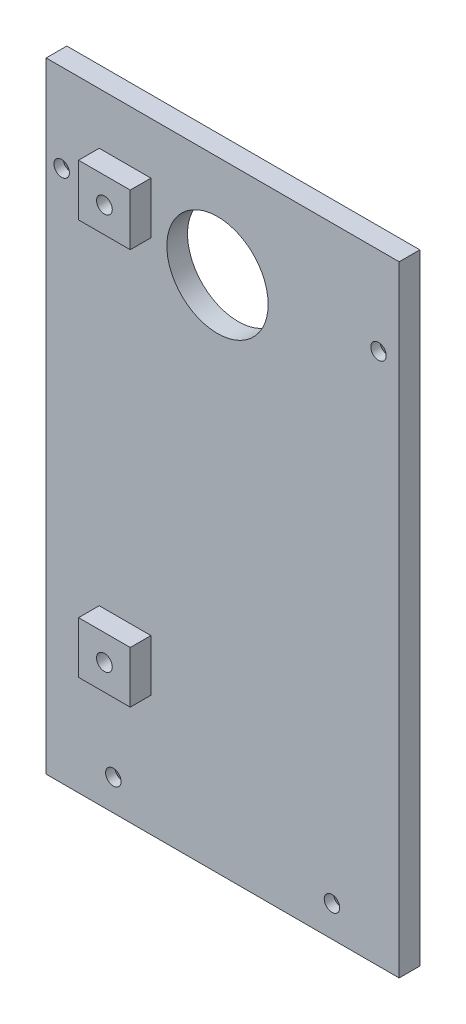
SolidWorks part; units mm, degrees
ref_plane "Front Plane" through (0, 0, 0) normal (0, 0, 1) x (1, 0, 0)
ref_plane "Top Plane" through (0, 0, 0) normal (0, 1, 0) x (1, 0, 0)
ref_plane "Right Plane" through (0, 0, 0) normal (1, 0, 0) x (0, 0, -1)
sketch "Sketch1" plane through (0, 0, 0) normal (0, 0, 1) x (1, 0, 0)
  line L0 (0, 0) -> (0, 30) construction
  line L1 (-16.575, -30) -> (16.575, -30)
  line L2 (-16.575, -30) -> (-16.575, 30)
  line L3 (-16.575, 30) -> (16.575, 30)
  line L4 (16.575, -30) -> (16.575, 30)
  line L5 (-16.575, -30) -> (16.575, 30) construction
  line L6 (-16.575, 30) -> (16.575, -30) construction
  line L7 (0, 25) -> (11.44, 25) construction
  line L8 (11.44, 25) -> (11.44, -18.32) construction
  circle A0 centre (0, 20.1) radius 4.9
  point P0 (0, 0)
  dimension "D3" = 9.8
  dimension "D1" = 33.15
  dimension "D2" = 60
  dimension "D4" = 11.44
  dimension "D5" = 43.32
extrude "Boss-Extrude1" add sketch "Sketch1" along normal blind 2
sketch "Sketch3" plane through (0, 0, 2) normal (0, 0, 1) x (1, 0, 0)
  line L0 (0, 25) -> (-11.44, 25) construction
  line L1 (-11.44, 25) -> (-11.44, -18.32) construction
  line L3 (-11.44, 25) -> (-6.44, 25)
  line L4 (-11.44, 25) -> (-11.44, 20)
  line L5 (-11.44, 20) -> (-6.44, 20)
  line L6 (-6.44, 25) -> (-6.44, 20)
  line L7 (-11.44, -18.32) -> (-6.44, -18.32)
  line L8 (-11.44, -18.32) -> (-11.44, -13.32)
  line L9 (-11.44, -13.32) -> (-6.44, -13.32)
  line L10 (-6.44, -18.32) -> (-6.44, -13.32)
  circle A0 centre (0, 20.1) radius 4.9 construction
  dimension "D1" = 11.44
  dimension "D2" = 43.32
  dimension "D3" = 5
  dimension "D4" = 5
  dimension "D5" = 5
  dimension "D6" = 5
extrude "Boss-Extrude2" add sketch "Sketch3" along normal blind 2
sketch "Sketch4" plane through (0, 0, 0) normal (0, 0, -1) x (-1, 0, 0)
  line L0 (-16.575, 30) -> (16.575, 30) construction
  line L1 (-16.575, -30) -> (-16.575, 30) construction
  line L2 (16.575, -30) -> (-16.575, -30) construction
  line L3 (16.575, 30) -> (16.575, -30) construction
  circle A0 centre (-15.575, 21.5) radius 0.75
  circle A1 centre (15.075, 21.5) radius 0.75
  circle A2 centre (10.075, -27) radius 0.75
  circle A3 centre (-11.075, -27) radius 0.75
  dimension "D3" = 1.5
  dimension "D4" = 1.5
  dimension "D5" = 1.5
  dimension "D6" = 1.5
  dimension "D1" = 8.5
  dimension "D2" = 1
  dimension "D7" = 3
  dimension "D8" = 5.5
  dimension "D9" = 6.5
  dimension "D10" = 8.5
extrude "Cut-Extrude1" cut sketch "Sketch4" against normal up to surface (2 mm away) up to face at (-8.94, 22.5, 2)
chamfer "Chamfer1" distance 1.1 angle 45 4 edges at (-10.825, -27, 0) (11.825, -27, 0) (-14.325, 21.5, 0) (14.825, 21.5, 0)
sketch "Sketch5" plane through (16.575, 0, 0) normal (1, 0, 0) x (0, 0, -1)
  line L1 (-2, 30) -> (0, 30)
  line L2 (-2, 30) -> (-2, -30)
  line L3 (-2, -30) -> (0, -30)
  line L4 (0, 30) -> (0, -30)
extrude "Boss-Extrude3" add sketch "Sketch5" along normal blind 1
ref_plane "Plane1" through (-16.575, 30, 0) normal (0, 0, -1) x (-1, 0, 0)
sketch "Sketch7" plane through (0, 0, 4) normal (0, 0, 1) x (1, 0, 0)
  line L1 (-6.44, 20) -> (-6.44, 25) construction
  line L2 (-6.44, 25) -> (-11.44, 25) construction
  line L3 (-6.44, -13.32) -> (-11.44, -13.32) construction
  line L4 (-6.44, -18.32) -> (-6.44, -13.32) construction
  circle A0 centre (-8.94, 22.5) radius 0.762
  circle A1 centre (-8.94, -15.82) radius 0.762
  point P12 (-10.7903, -14.6884)
  dimension "D5" = 1.524
  dimension "D6" = 1.524
  dimension "D1" = 2.5
  dimension "D2" = 2.5
  dimension "D3" = 2.5
  dimension "D4" = 2.5
extrude "Cut-Extrude2" cut sketch "Sketch7" against normal blind 3.5
